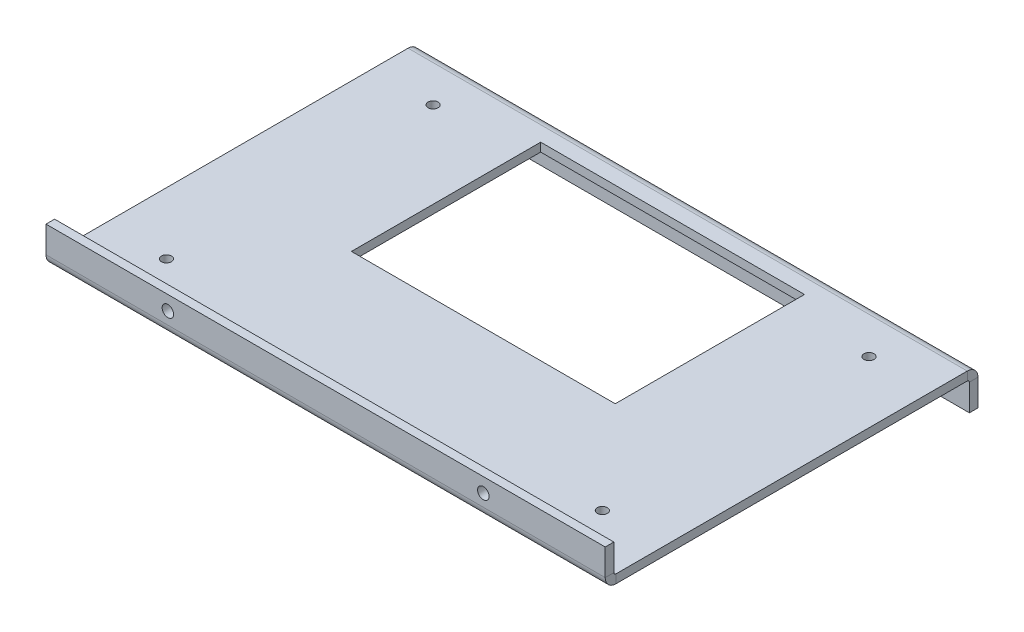
SolidWorks part; units mm, degrees
note: The reader was unsure of these and kept them because the rebuilt part matched: flange length of "边线-法兰1", "边线-法兰2".
ref_plane "前视基准面" through (0, 0, 0) normal (0, 0, 1) x (1, 0, 0)
ref_plane "上视基准面" through (0, 0, 0) normal (0, 1, 0) x (1, 0, 0)
ref_plane "右视基准面" through (0, 0, 0) normal (1, 0, 0) x (0, 0, -1)
sketch "草图1" plane through (0, 0, 0) normal (0, 1, 0) x (1, 0, 0)
  line L1 (-97.5, -65) -> (97.5, -65)
  line L2 (-97.5, -65) -> (-97.5, 65)
  line L3 (-97.5, 65) -> (97.5, 65)
  line L4 (97.5, -65) -> (97.5, 65)
  line L5 (-97.5, -65) -> (97.5, 65) construction
  line L6 (-97.5, 65) -> (97.5, -65) construction
  point P0 (0, 0)
  dimension "D1" = 130
  dimension "D2" = 195
base flange "基体-法兰1" sketch "草图1" thickness 3 reverse thickness direction no parameters "D1"=0.7366
edge flange "边线-法兰1" sketch "草图8" flange angle 90 flange length 10 flange position material inside bend radius 0.7366 thickness 3 relief rectangular parameters "D6"=10
sketch "草图8" plane through (0, 0, 65) normal (0, 0, 1) x (1, 0, 0)
  line L2 (-97.5, 0) -> (-97.5, 10)
  line L3 (-97.5, 10) -> (97.5, 10)
  line L4 (97.5, 10) -> (97.5, 0)
  line L7 (-97.5, 0) -> (97.5, 0) construction
  line L8 (-97.5, 0) -> (97.5, 0)
bend "边线折弯1" bend radius 0.7366 bend angle 90 parameters "D5"=1
edge flange "边线-法兰2" sketch "草图11" flange angle 90 flange length 10 flange position material inside bend radius 0.7366 thickness 3 relief rectangular parameters "D6"=10
sketch "草图11" plane through (0, -3, -65) normal (0, 0, -1) x (1, 0, 0)
  line L0 (97.5, 0) -> (-97.5, 0) construction
  line L1 (97.5, 0) -> (-97.5, 0)
  line L2 (-97.5, 0) -> (-97.5, 10)
  line L3 (-97.5, 10) -> (97.5, 10)
  line L4 (97.5, 10) -> (97.5, 0)
bend "边线折弯2" bend radius 0.7366 bend angle 90 parameters "D5"=2
sketch "草图12" plane through (0, 0, 65) normal (0, 0, 1) x (1, 0, 0)
  line L0 (0, 10) -> (0, 0) construction
  line L1 (97.5, 10) -> (-97.5, 10) construction
  circle A0 centre (-55, 5) radius 2
  circle A1 centre (55, 5) radius 2
  dimension "D1" = 4
  dimension "D2" = 5
  dimension "D3" = 110
extrude "切除-拉伸1" cut sketch "草图12" against normal blind 10 normal cut yes
sketch "草图13" plane through (0, 0, -65) normal (0, 0, -1) x (-1, 0, 0)
  line L0 (0, -3.7366) -> (0, -13) construction
  line L1 (-97.5, -3.7366) -> (97.5, -3.7366) construction
  line L2 (-97.5, -13) -> (97.5, -13) construction
  circle A0 centre (-55, -8) radius 2
  circle A1 centre (55, -8) radius 2
  dimension "D1" = 4
  dimension "D2" = 5
  dimension "D3" = 110
extrude "切除-拉伸2" cut sketch "草图13" against normal blind 10 normal cut yes
sketch "草图14" plane through (0, 0, 0) normal (0, 1, 0) x (1, 0, 0)
  line L0 (-82.5, -51) -> (82.5, -51) construction
  line L5 (-82.5, -55) -> (82.5, -55) construction
  line L6 (-82.5, -55) -> (-82.5, 55) construction
  line L7 (-82.5, 55) -> (82.5, 55) construction
  line L8 (82.5, -55) -> (82.5, 55) construction
  line L9 (-82.5, -55) -> (82.5, 55) construction
  line L10 (-82.5, 55) -> (82.5, -55) construction
  line L11 (0, 55) -> (0, -55) construction
  line L12 (-82.5, 2) -> (82.5, 2) construction
  line L14 (46, -10) -> (-46, -10)
  line L15 (46, -10) -> (46, 56)
  line L16 (46, 56) -> (-46, 56)
  line L17 (-46, -10) -> (-46, 56)
  line L18 (46, -10) -> (-46, 56) construction
  line L19 (46, 56) -> (-46, -10) construction
  circle A0 centre (-76, 48.5) radius 1.75
  circle A1 centre (76, 48.5) radius 1.75
  circle A2 centre (76, -44.5) radius 1.75
  circle A3 centre (-76, -44.5) radius 1.75
  point P4 (0, 0)
  point P24 (0, 23)
  point P29 (0, 0)
  dimension "D5" = 3.5
  dimension "D1" = 165
  dimension "D2" = 110
  dimension "D3" = 6.5
  dimension "D4" = 6.5
  dimension "D6" = 4
  dimension "D7" = 53
  dimension "D8" = 92
  dimension "D9" = 66
  dimension "D10" = 1
extrude "切除-拉伸3" cut sketch "草图14" against normal up to next normal cut yes
sketch "折弯-线1" plane through (0, 0, 0) normal (0, 1, 0) x (1, 0, 0)
sketch "边界框1" plane through (0, 0, 0) normal (0, 1, 0) x (1, 0, 0)
sheet metal parameters "钣金6" thickness 3 parameters "D1"=0.7366
flat pattern "平板型式6" [suppressed]
sketch "折弯-线2" plane through (0, 0, 0) normal (0, 1, 0) x (1, 0, 0)
sketch "边界框2" [suppressed] plane through (0, 0, 0) normal (0, 1, 0) x (1, 0, 0)
sheet metal parameters "钣金7" thickness 3 parameters "D1"=0.7366
flat pattern "平板型式6" [suppressed]
sketch "折弯-线2" plane through (0, 0, 0) normal (0, 1, 0) x (1, 0, 0)
sketch "边界框2" [suppressed] plane through (0, 0, 0) normal (0, 1, 0) x (1, 0, 0)
bend of the flat pattern "展平-<边线折弯1>1"
sheet metal parameters "钣金8" thickness 3 parameters "D1"=0.7366
flat pattern "平板型式6" [suppressed]
sketch "折弯-线2" plane through (0, 0, 0) normal (0, 1, 0) x (1, 0, 0)
sketch "边界框2" [suppressed] plane through (0, 0, 0) normal (0, 1, 0) x (1, 0, 0)
bend of the flat pattern "展平-<边线折弯1>1"
bend of the flat pattern "展平-<边线折弯2>1"
sheet metal parameters "钣金9" thickness 3 parameters "D1"=0.7366
flat pattern "平板型式6" [suppressed]
sketch "折弯-线2" plane through (0, 0, 0) normal (0, 1, 0) x (1, 0, 0)
sketch "边界框2" [suppressed] plane through (0, 0, 0) normal (0, 1, 0) x (1, 0, 0)
bend of the flat pattern "展平-<边线折弯1>1"
bend of the flat pattern "展平-<边线折弯2>1"
sheet metal parameters "钣金10" thickness 3 parameters "D1"=0.7366
flat pattern "平板型式6" [suppressed]
sketch "折弯-线2" plane through (0, 0, 0) normal (0, 1, 0) x (1, 0, 0)
sketch "边界框2" [suppressed] plane through (0, 0, 0) normal (0, 1, 0) x (1, 0, 0)
bend of the flat pattern "展平-<边线折弯1>1"
bend of the flat pattern "展平-<边线折弯2>1"
sheet metal parameters "钣金11" thickness 3 parameters "D1"=0.7366
flat pattern "平板型式6" [suppressed]
sketch "折弯-线2" plane through (0, 0, 0) normal (0, 1, 0) x (1, 0, 0)
sketch "边界框2" [suppressed] plane through (0, 0, 0) normal (0, 1, 0) x (1, 0, 0)
bend of the flat pattern "展平-<边线折弯1>1"
bend of the flat pattern "展平-<边线折弯2>1"
